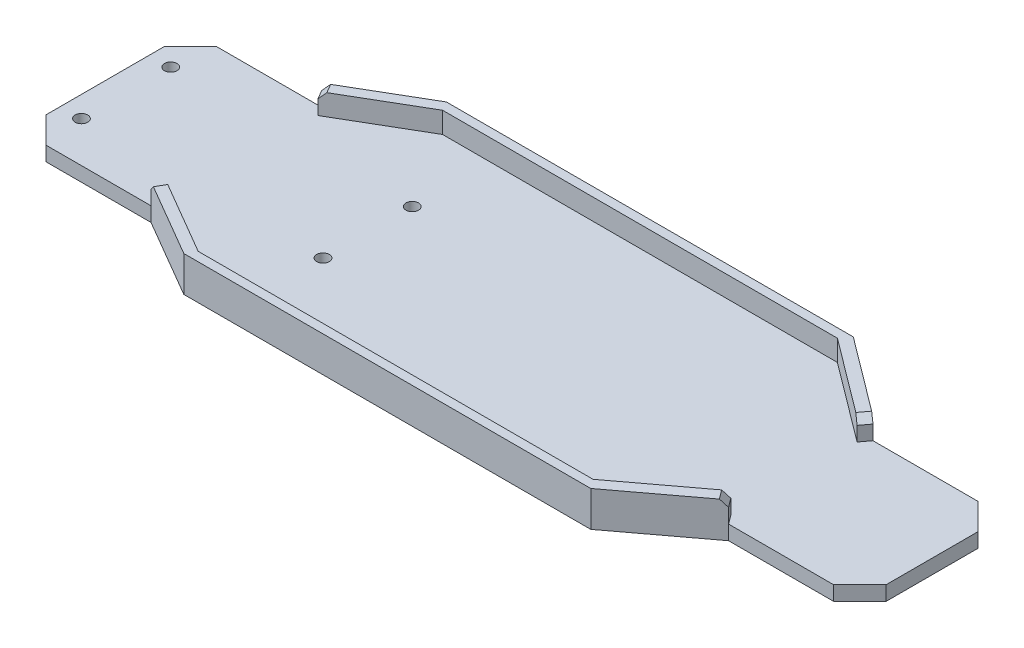
SolidWorks part; units mm, degrees
material "PETG - Polymaker"
ref_plane "Front Plane" through (0, 0, 0) normal (0, 0, 1) x (1, 0, 0)
ref_plane "Top Plane" through (0, 0, 0) normal (0, 1, 0) x (1, 0, 0)
ref_plane "Right Plane" through (0, 0, 0) normal (1, 0, 0) x (0, 0, -1)
sketch "Sketch1" plane through (0, 0, 0) normal (0, 1, 0) x (1, 0, 0)
  line L0 (-235.1499, 0) -> (235.1499, 0) construction
  line L1 (0, 0) -> (0, 52596.8311) construction
  line L2 (-107.5, 32.5) -> (-77.5, 50)
  line L3 (-77.5, 50) -> (77.5, 50)
  line L4 (-107.5, 32.5) -> (-157.5, 32.5)
  line L5 (-157.5, 32.5) -> (-157.5, -32.5)
  line L6 (-77.5, -50) -> (77.5, -50)
  line L7 (-107.5, -32.5) -> (-77.5, -50)
  line L8 (-107.5, -32.5) -> (-157.5, -32.5)
  line L9 (77.5, 50) -> (107.5, 27.5)
  line L10 (107.5, 27.5) -> (157.5, 27.5)
  line L11 (157.5, 27.5) -> (157.5, -27.5)
  line L12 (107.5, -27.5) -> (157.5, -27.5)
  line L13 (77.5, -50) -> (107.5, -27.5)
  point P3 (0, 0)
  point P10 (-92.5, 41.25)
  point P15 (-92.5, -41.25)
  point P18 (-157.5, 0)
  point P19 (0, -50)
  point P20 (0, 50)
  point P23 (157.5, 0)
  dimension "D1" = 50
  dimension "D2" = 65
  dimension "D3" = 30
  dimension "D4" = 50
  dimension "D5" = 155
  dimension "D6" = 50
  dimension "D7" = 55
  dimension "D8" = 30
extrude "Boss-Extrude1" add sketch "Sketch1" along normal blind 5.5
sketch "Sketch3" plane through (0, 5.5, 0) normal (0, 1, 0) x (1, 0, 0)
  line L0 (0, 0) -> (50000, 0) construction
  line L1 (0, 0) -> (0, 50000) construction
  line L2 (0, 50) -> (-77.5, 50)
  line L3 (77.5, 50) -> (-77.5, 50) construction
  line L4 (-77.5, 50) -> (-107.5, 32.5)
  line L5 (-107.5, 32.5) -> (-105.4845, 29.0449)
  line L6 (-105.4845, 29.0449) -> (-75.4845, 46.5449)
  line L7 (-75.4845, 46.5449) -> (0, 46.5449)
  line L8 (-77.5, 50) -> (-75.4845, 46.5449) construction
  line L9 (0, 50) -> (77.5, 50)
  line L10 (77.5, 50) -> (107.5, 27.5)
  line L11 (107.5, 27.5) -> (104.9087, 24.0449)
  line L12 (104.9087, 24.0449) -> (74.9087, 46.5449)
  line L13 (74.9087, 46.5449) -> (0, 46.5449)
  line L14 (74.9087, 46.5449) -> (77.5, 50) construction
  line L15 (74.9087, -46.5449) -> (77.5, -50) construction
  line L16 (-77.5, -50) -> (-75.4845, -46.5449) construction
  line L17 (74.9087, -46.5449) -> (0, -46.5449)
  line L18 (104.9087, -24.0449) -> (74.9087, -46.5449)
  line L19 (107.5, -27.5) -> (104.9087, -24.0449)
  line L20 (77.5, -50) -> (107.5, -27.5)
  line L21 (0, -50) -> (77.5, -50)
  line L22 (-75.4845, -46.5449) -> (0, -46.5449)
  line L23 (-105.4845, -29.0449) -> (-75.4845, -46.5449)
  line L24 (-107.5, -32.5) -> (-105.4845, -29.0449)
  line L25 (-77.5, -50) -> (-107.5, -32.5)
  line L26 (0, -50) -> (-77.5, -50)
  dimension "D1" = 4
extrude "Chassis-Walls1" add sketch "Sketch3" along normal blind 8
chamfer "Chamfer1" distance 10 angle 45 2 edges at (-157.5, 2.75, -32.5) (-157.5, 2.75, 32.5)
chamfer "Chamfer2" distance 10 angle 45 2 edges at (157.5, 2.75, -27.5) (157.5, 2.75, 27.5)
chamfer "Chamfer3" distance 2.5 angle 45 4 edges at (-106.4923, 13.5, -30.7724) (-106.4923, 13.5, 30.7724) (106.2043, 13.5, 25.7724) (106.2043, 13.5, -25.7724)
sketch "Sketch4" plane through (0, 0, 0) normal (0, -1, 0) x (1, 0, 0)
  line L0 (0, 0) -> (50000, 0) construction
  line L1 (-149.5, 17) -> (-57.5, 17) construction
  line L2 (-157.5, -22.5) -> (-157.5, 22.5) construction
  circle A0 centre (-149.5, 17) radius 2.4
  circle A1 centre (-57.5, 17) radius 2.4
  circle A2 centre (-57.5, -17) radius 2.4
  circle A3 centre (-149.5, -17) radius 2.4
  point P9 (0, 0)
  dimension "D1" = 4.8
  dimension "D2" = 4.8
  dimension "D3" = 8
  dimension "D4" = 92
  dimension "D5" = 34
extrude "Cut-Extrude1" cut sketch "Sketch4" against normal blind 10
